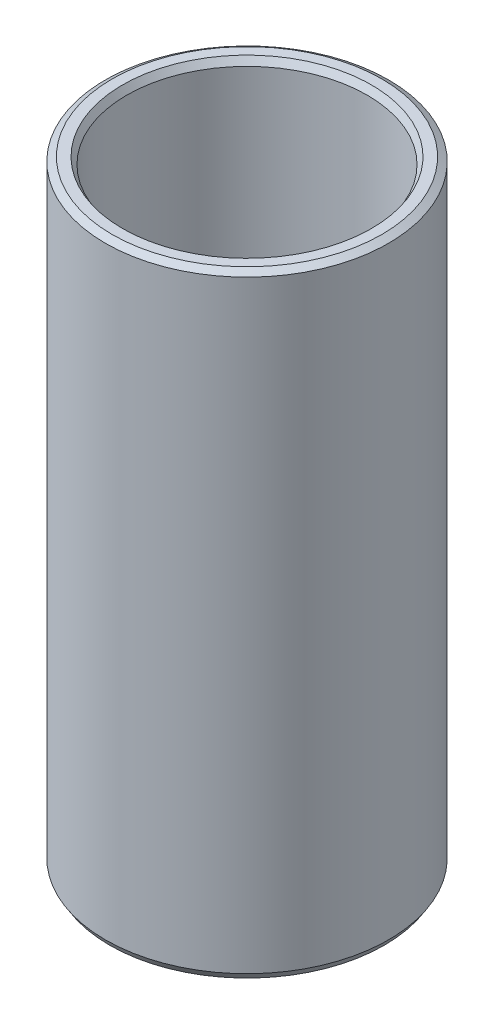
SolidWorks part; units mm, degrees
ref_plane "Front Plane" through (0, 0, 0) normal (0, 0, 1) x (1, 0, 0)
ref_plane "Top Plane" through (0, 0, 0) normal (0, 1, 0) x (1, 0, 0)
ref_plane "Right Plane" through (0, 0, 0) normal (1, 0, 0) x (0, 0, -1)
sketch "Sketch1" plane through (0, 0, 0) normal (0, 1, 0) x (1, 0, 0)
  circle A0 centre (0, 0) radius 22.5
  dimension "SLEEVE_OD" = 45
extrude "Boss-Extrude1" add sketch "Sketch1" along normal blind 97.6144
sketch "Sketch2" plane through (0, 0, 0) normal (0, 1, 0) x (1, 0, 0)
  circle A0 centre (0, 0) radius 19.1104
  dimension "BORE_D" = 38.2207
extrude "Cut-Extrude1" cut sketch "Sketch2" along normal through all
chamfer "Chamfer1" distance 0.669 angle 58.153 4 edges at (0, 97.6144, 19.1104) (0, 0, 19.1104) (0, 0, 22.5) (0, 97.6144, 22.5) first distance on face at (0, 97.6144, 19.1104) first distance on face at (0, 0, 19.1104) first distance on face at (0, 97.6144, 22.5)
